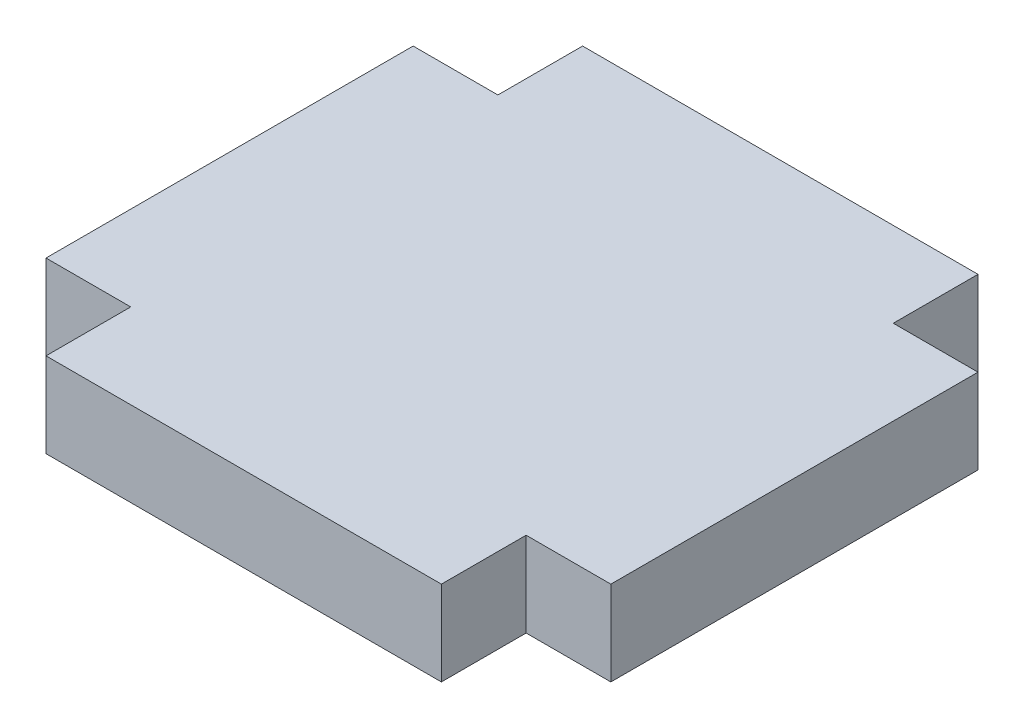
SolidWorks part; units mm, degrees
ref_plane "Alzado" through (0, 0, 0) normal (0, 0, 1) x (1, 0, 0)
ref_plane "Planta" through (0, 0, 0) normal (0, 1, 0) x (1, 0, 0)
ref_plane "Vista lateral" through (0, 0, 0) normal (1, 0, 0) x (0, 0, -1)
sketch "Croquis1" plane through (0, 0, 0) normal (0, 1, 0) x (1, 0, 0)
  line L0 (0, 0) -> (0, 13)
  line L1 (0, 13) -> (3, 13)
  line L2 (20, 13) -> (20, 0)
  line L3 (20, 0) -> (17, 0)
  line L4 (3, 0) -> (0, 0)
  line L5 (3, 16) -> (17, 16)
  line L6 (17, 16) -> (17, 13)
  line L7 (3, 16) -> (3, 13)
  line L8 (10, 16) -> (10, -3) construction
  line L9 (3, -3) -> (3, 0)
  line L10 (17, -3) -> (17, 0)
  line L11 (3, -3) -> (17, -3)
  line L12 (0, 6.5) -> (20, 6.5) construction
  line L13 (17, 13) -> (20, 13)
  dimension "D1" = 13
  dimension "D2" = 20
  dimension "D3" = 3
  dimension "D4" = 3
  dimension "D5" = 7
  dimension "D6" = 3
  dimension "D7" = 14
  dimension "D8" = 3
  dimension "D9" = 14
  dimension "D10" = 19
  dimension "D11" = 3
extrude "Saliente-Extruir1" add sketch "Croquis1" along normal blind 3
